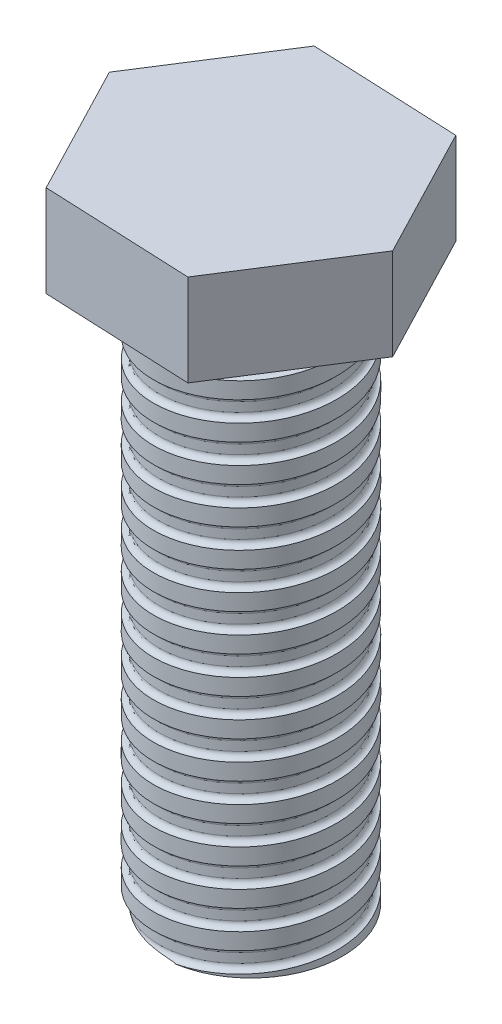
SolidWorks part; units mm, degrees
ref_plane "Front Plane" through (0, 0, 0) normal (0, 0, 1) x (1, 0, 0)
ref_plane "Top Plane" through (0, 0, 0) normal (0, 1, 0) x (1, 0, 0)
ref_plane "Right Plane" through (0, 0, 0) normal (1, 0, 0) x (0, 0, -1)
sketch "Sketch1" plane through (0, 0, 0) normal (0, 1, 0) x (1, 0, 0)
  circle A0 centre (0, 0) radius 5
extrude "Boss-Extrude1" add sketch "Sketch1" along normal blind 30
sketch "Sketch2" plane through (0, 30, 0) normal (0, 1, 0) x (1, 0, 0)
  line L1 (-4.3444, -6.8161) -> (3.7308, -7.1704)
  line L2 (3.7308, -7.1704) -> (8.0751, -0.3543)
  line L3 (8.0751, -0.3543) -> (4.3444, 6.8161)
  line L4 (4.3444, 6.8161) -> (-3.7308, 7.1704)
  line L5 (-3.7308, 7.1704) -> (-8.0751, 0.3543)
  line L6 (-8.0751, 0.3543) -> (-4.3444, -6.8161)
  circle A0 centre (0, 0) radius 7 construction
extrude "Boss-Extrude2" add sketch "Sketch2" along normal blind 5
sketch "Sketch3" plane through (0, 0, 0) normal (0, -1, 0) x (-1, 0, 0)
  circle A0 centre (0, 0) radius 5
curve "Helix/Spiral2" pitch 2 height 30 turns 15
ref_plane "Plane1" through (-5, 0, 0) normal (0, 0.0635, 0.998) x (1, 0, 0)
sketch "Sketch4" plane through (-5, 0, 0) normal (0, 0.0635, 0.998) x (1, 0, 0)
  line L0 (0, -0.25) -> (0, 0.25) construction
  line L1 (-0.3, -0.25) -> (-0.3, 0.25)
  line L2 (0.3, -0.25) -> (0.3, 0.25)
  arc A0 (-0.3, -0.25) -> (0.3, -0.25) centre (0, -0.25) ccw
  arc A1 (0.3, 0.25) -> (-0.3, 0.25) centre (0, 0.25) ccw
  point P2 (0, 0)
  point P7 (0, 0)
  dimension "D1" = 0.3
  dimension "D2" = 0.5
sweep "Cut-Sweep2" cut profiles "Sketch4" path "Helix/Spiral2" align with end faces yes
